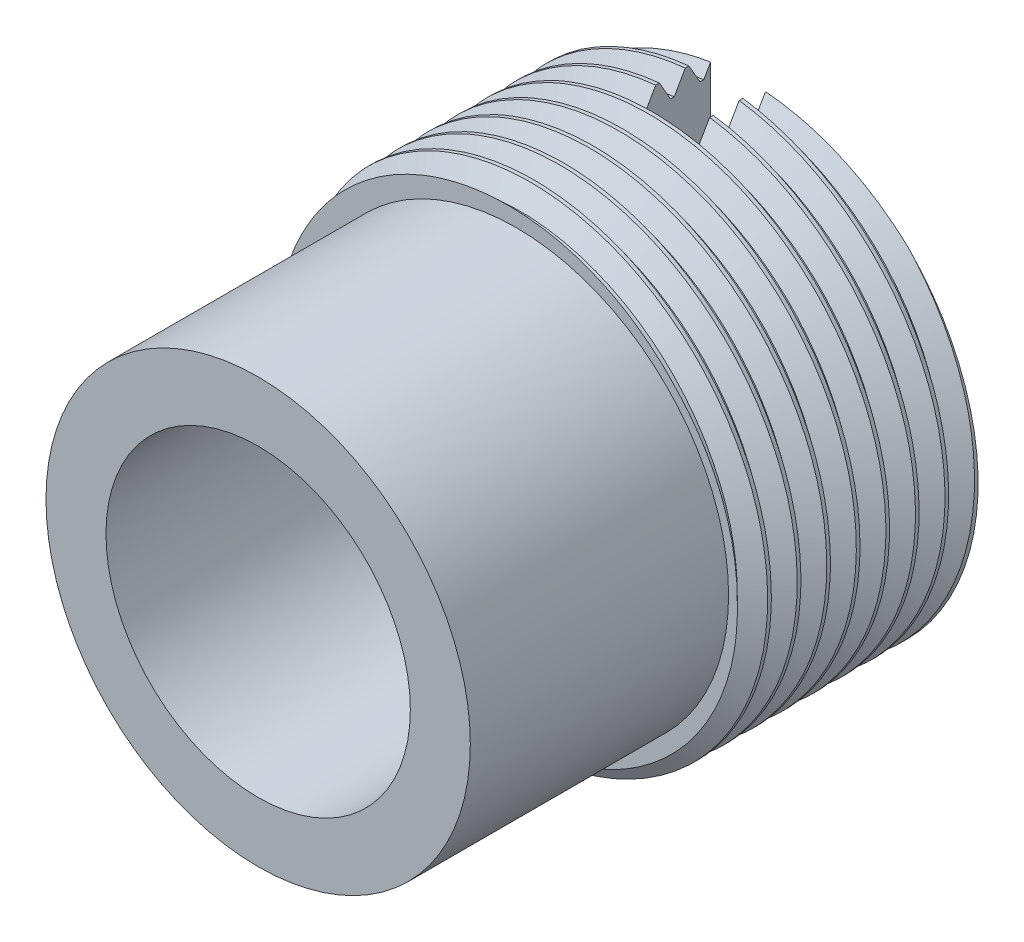
SolidWorks part; units mm, degrees
ref_plane "Front" through (0, 0, 0) normal (0, 0, 1) x (1, 0, 0)
ref_plane "Top" through (0, 0, 0) normal (0, 1, 0) x (1, 0, 0)
ref_plane "Right" through (0, 0, 0) normal (1, 0, 0) x (0, 0, -1)
sketch "Sketch1" plane through (0, 0, 0) normal (0, 0, 1) x (1, 0, 0)
  circle A0 centre (0, 0) radius 6.5405
  circle A1 centre (0, 0) radius 10.3187
  dimension "D1" = 20.6375
  dimension "D2" = 13.081
extrude "Boss-Extrude1" add sketch "Sketch1" along normal blind 10.795
thread "Thread6" start angle 0, offset 0, length 10.16, pitch 1.27, diameter 20.6375
ref_plane "Plane11" through (-10.3187, 0, 10.795) normal (0, -1, 0) x (-1, 0, 0)
sketch "Thread Profile11" plane through (-10.3187, 0, 10.795) normal (0, -1, 0) x (-1, 0, 0)
  line L0 (0, 0) -> (0, 1.27) construction
  line L11 (0, 0) -> (0, 1.1132)
  line L12 (0, 1.1132) -> (-0.8255, 0.6366)
  line L13 (-0.8255, 0.6366) -> (-0.8255, 0.4766)
  line L15 (-0.8255, 0.4766) -> (0, 0)
  line L17 (-0.8255, 0.5566) -> (0, 0.5566) construction
  point P2 (0, 0)
  dimension "Pitch" = 1.27
  dimension "Profile_Angle" = 60
  dimension "Profile_Land" = 0.16
  dimension "Profile_Height" = 0.8255
sketch "Sketch39" plane through (0, 0, 10.795) normal (0, 0, 1) x (1, 0, 0)
  circle A0 centre (0, 0) radius 10.3187 construction
  circle A1 centre (0, 0) radius 10.3187
extrude "Cut-Extrude1" cut sketch "Sketch39" against normal blind 1.27
sketch "Sketch41" plane through (0, 0, 9.525) normal (0, 0, 1) x (1, 0, 0)
  circle A0 centre (0, 0) radius 9.1186
  circle A1 centre (0, 0) radius 6.5405 construction
  circle A2 centre (0, 0) radius 6.5405
  dimension "D1" = 18.2372
extrude "Boss-Extrude2" add sketch "Sketch41" along normal blind 11.0998
sketch "Sketch42" plane through (0, 0, 0) normal (0, 0, -1) x (-1, 0, 0)
  line L0 (0, 11.9233) -> (0, -11.9233) construction
  line L1 (-1.1811, 11.9233) -> (-1.1811, -11.9233)
  line L2 (1.1811, 11.9233) -> (1.1811, -11.9233)
  line L3 (-1.1811, -11.9233) -> (1.1811, -11.9233)
  line L4 (-1.1811, 11.9233) -> (1.1811, 11.9233)
  point P5 (0, 0)
  dimension "D3" = 11.9233
  dimension "D1" = 1.1811
  dimension "D2" = 1.1811
extrude "Cut-Extrude2" cut sketch "Sketch42" against normal blind 3.175
